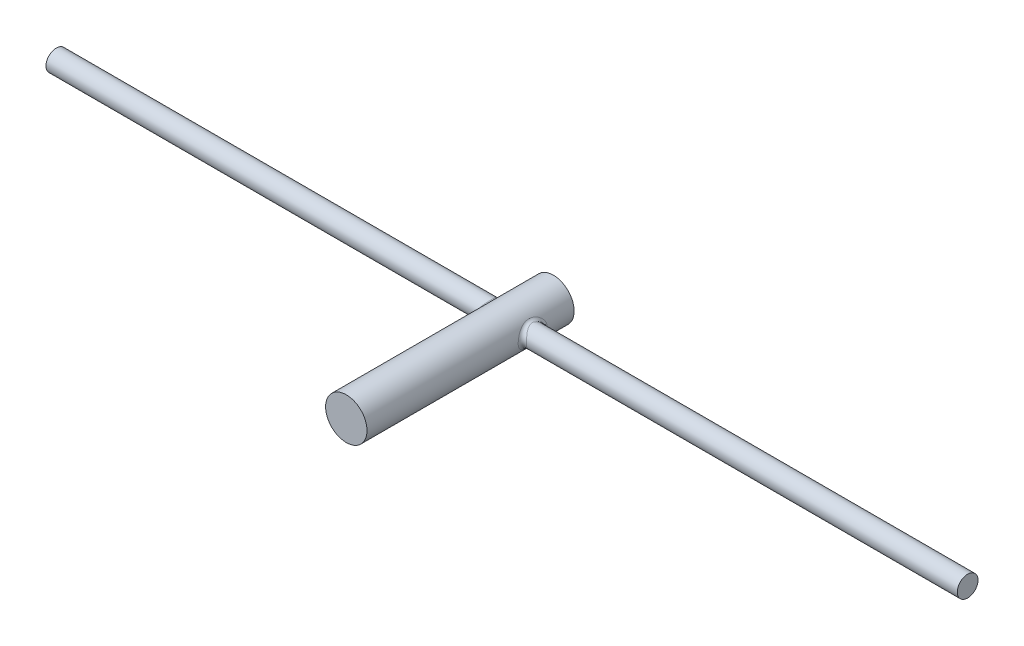
SolidWorks part; units mm, degrees
ref_plane "Front Plane" through (0, 0, 0) normal (0, 0, 1) x (1, 0, 0)
ref_plane "Top Plane" through (0, 0, 0) normal (0, 1, 0) x (1, 0, 0)
ref_plane "Right Plane" through (0, 0, 0) normal (1, 0, 0) x (0, 0, -1)
sketch "Sketch1" plane through (0, 0, 0) normal (0, 0, 1) x (1, 0, 0)
  circle A0 centre (0, 0) radius 5
  dimension "D1" = 10
extrude "Boss-Extrude1" add sketch "Sketch1" along normal blind 50
sketch "Sketch2" plane through (0, 0, 0) normal (1, 0, 0) x (0, 0, -1)
  line L0 (5.5, 0) -> (-5.5, 0) construction
  line L1 (0, 5.5) -> (0, -5.5) construction
  circle A0 centre (-10, 0) radius 2.5
  dimension "D1" = 5
  dimension "D2" = 10
extrude "Boss-Extrude2" add sketch "Sketch2" along normal blind 110 and the other way blind 110 contours A0
fillet "Fillet1" radius 1 2 edges at (-4.9936, 0.2523, 7.5128) (4.9936, 0.2523, 12.4872)
